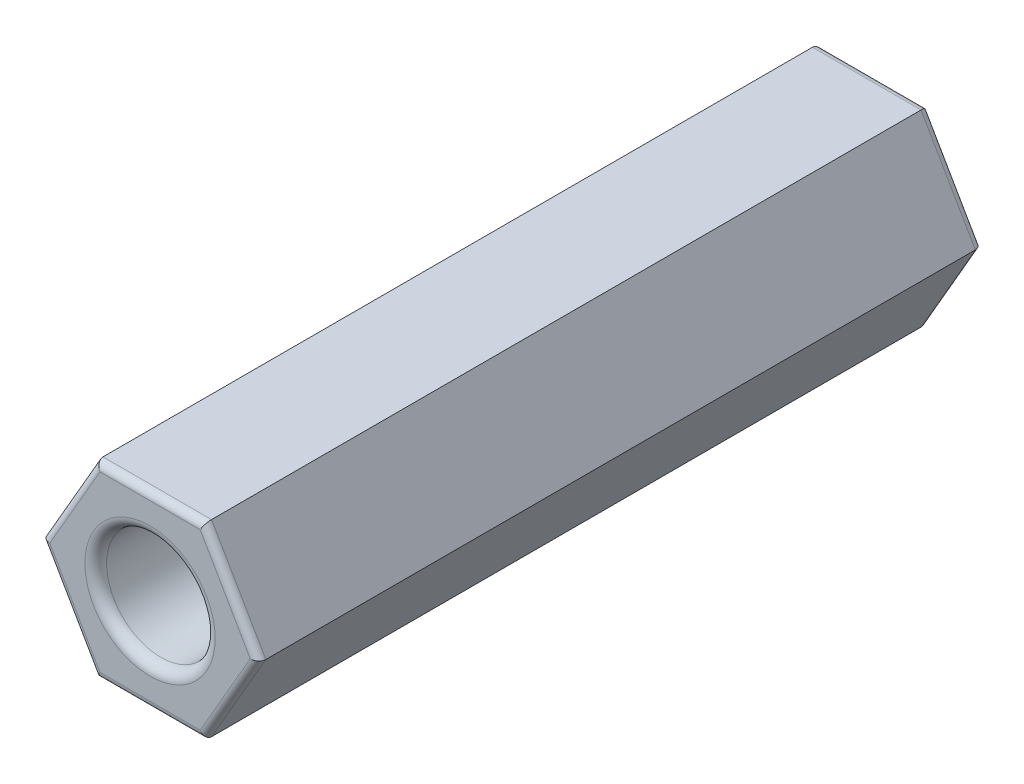
SolidWorks part; units mm, degrees
ref_plane "Front Plane" through (0, 0, 0) normal (0, 0, 1) x (1, 0, 0)
ref_plane "Top Plane" through (0, 0, 0) normal (0, 1, 0) x (1, 0, 0)
ref_plane "Right Plane" through (0, 0, 0) normal (1, 0, 0) x (0, 0, -1)
ref_axis "Axis1" through (0, 0, -81.49) along (0, 0, 1)
sketch "Sketch1" plane through (0, 0, 0) normal (0, 0, 1) x (1, 0, 0)
  line L1 (3, 0) -> (1.5, 2.5981)
  line L2 (1.5, 2.5981) -> (-1.5, 2.5981)
  line L3 (-1.5, 2.5981) -> (-3, 0)
  line L4 (-3, 0) -> (-1.5, -2.5981)
  line L5 (-1.5, -2.5981) -> (1.5, -2.5981)
  line L6 (1.5, -2.5981) -> (3, 0)
  circle A0 centre (0, 0) radius 2.5981 construction
  circle A1 centre (0, 0) radius 1.5
  dimension "D2" = 3
  dimension "D1" = 6
extrude "Boss-Extrude1" add sketch "Sketch1" along normal blind 20
fillet "Fillet1" radius 0.3 2 edges at (1.5, 0, 0) (1.5, 0, 20)
fillet "Fillet2" radius 0.2 12 edges at (-2.25, 1.299, 20) (-2.25, -1.299, 20) (0, -2.5981, 20) (2.25, -1.299, 20) (2.25, 1.299, 20) (0, 2.5981, 20) (2.25, -1.299, 0) (0, -2.5981, 0) (-2.25, -1.299, 0) (-2.25, 1.299, 0) (0, 2.5981, 0) (2.25, 1.299, 0)
sketch "Sketch2" plane through (0, 0, 0) normal (0, 0, 1) x (1, 0, 0)
  circle A0 centre (0, 0) radius 3 construction
